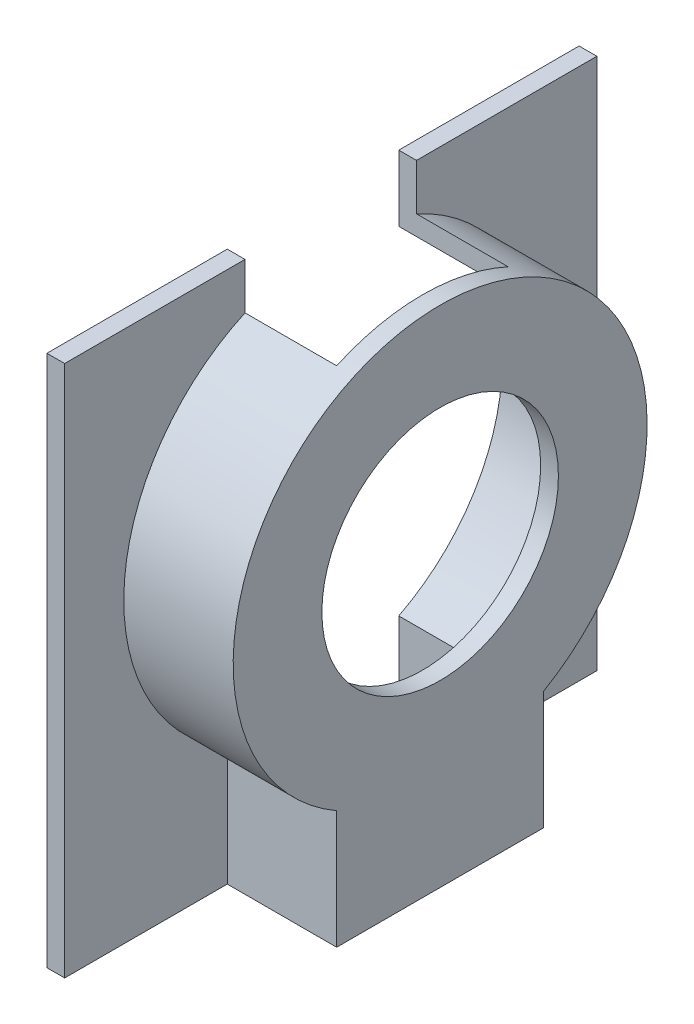
SolidWorks part; units mm, degrees
ref_plane "Front Plane" through (0, 0, 0) normal (0, 0, 1) x (1, 0, 0)
ref_plane "Top Plane" through (0, 0, 0) normal (0, 1, 0) x (1, 0, 0)
ref_plane "Right Plane" through (0, 0, 0) normal (1, 0, 0) x (0, 0, -1)
sketch "Sketch2" plane through (0, 0, 0) normal (1, 0, 0) x (0, 0, -1)
  line L1 (-9, -9) -> (9, -9)
  line L2 (-9, -9) -> (-9, 9)
  line L3 (-9, 9) -> (9, 9)
  line L4 (9, -9) -> (9, 9)
  line L5 (-9, -9) -> (9, 9) construction
  line L6 (-9, 9) -> (9, -9) construction
  point P0 (0, 0)
  dimension "D1" = 18
  dimension "D2" = 18
extrude "Boss-Extrude1" add sketch "Sketch2" along normal blind 4.3
sketch "Sketch4" plane through (4.3, 0, 0) normal (1, 0, 0) x (0, 0, -1)
  line L0 (-9, 0) -> (9, 0) construction
  line L1 (-9, 9) -> (-9, -9) construction
  line L2 (9, -9) -> (9, 9) construction
  line L3 (0, 9) -> (0, -9) construction
  line L4 (9, 9) -> (-9, 9) construction
  line L5 (-9, -9) -> (9, -9) construction
  line L7 (-3.5, -9) -> (3.5, -9)
  line L8 (-3.5, -9) -> (-3.5, -5)
  line L10 (3.5, -9) -> (3.5, -5)
  line L11 (-3.5, -9) -> (0, -5.9378) construction
  line L12 (0, -5.9378) -> (3.5, -9) construction
  arc A0 (3.5, -5) -> (-3.5, -5) centre (0, 1.0622) ccw
  point P14 (0, -5.9378)
  dimension "D1" = 14
  dimension "D2" = 7
  dimension "D3" = 4
extrude "Boss-Extrude2" add sketch "Sketch4" along normal blind 3.7
shell "Shell2" thickness 0.6 removed face at (0, 0, 0)
sketch "Sketch5" plane through (8, 0, 0) normal (1, 0, 0) x (0, 0, -1)
  line L0 (-7, 1.0622) -> (7, 1.0622) construction
  arc A0 (3.5, -5) -> (-3.5, -5) centre (0, 1.0622) ccw construction
  arc A1 (3.5, -5) -> (-3.5, -5) centre (0, 1.0622) ccw construction
  circle A2 centre (0, 1.0622) radius 4
  dimension "D1" = 8
extrude "Cut-Extrude1" cut sketch "Sketch5" against normal through all
sketch "Sketch6" plane through (0, -9, 0) normal (0, 1, 0) x (1, 0, 0)
  line L1 (0, 8.4) -> (0, -8.4)
  line L3 (3.7, -8.4) -> (3.7, -2.9)
  line L4 (3.7, -2.9) -> (7.4, -2.9)
  line L5 (7.4, -2.9) -> (7.4, 2.9)
  line L6 (7.4, 2.9) -> (3.7, 2.9)
  line L7 (3.7, 2.9) -> (3.7, 8.4)
  line L8 (0, 8.4) -> (0, 9)
  line L9 (0, 9) -> (3.7, 9)
  line L10 (4.3, 9) -> (0, 9) construction
  line L11 (3.7, 9) -> (3.7, 8.4)
  line L12 (0, -8.5743) -> (0, -9)
  line L13 (0, 9) -> (0, -9) construction
  line L14 (0, -9) -> (3.7, -9)
  line L15 (4.3, -9) -> (0, -9) construction
  line L16 (3.7, -9) -> (3.7, -8.4)
extrude "Cut-Extrude2" cut sketch "Sketch6" along normal through all and the other way through all
